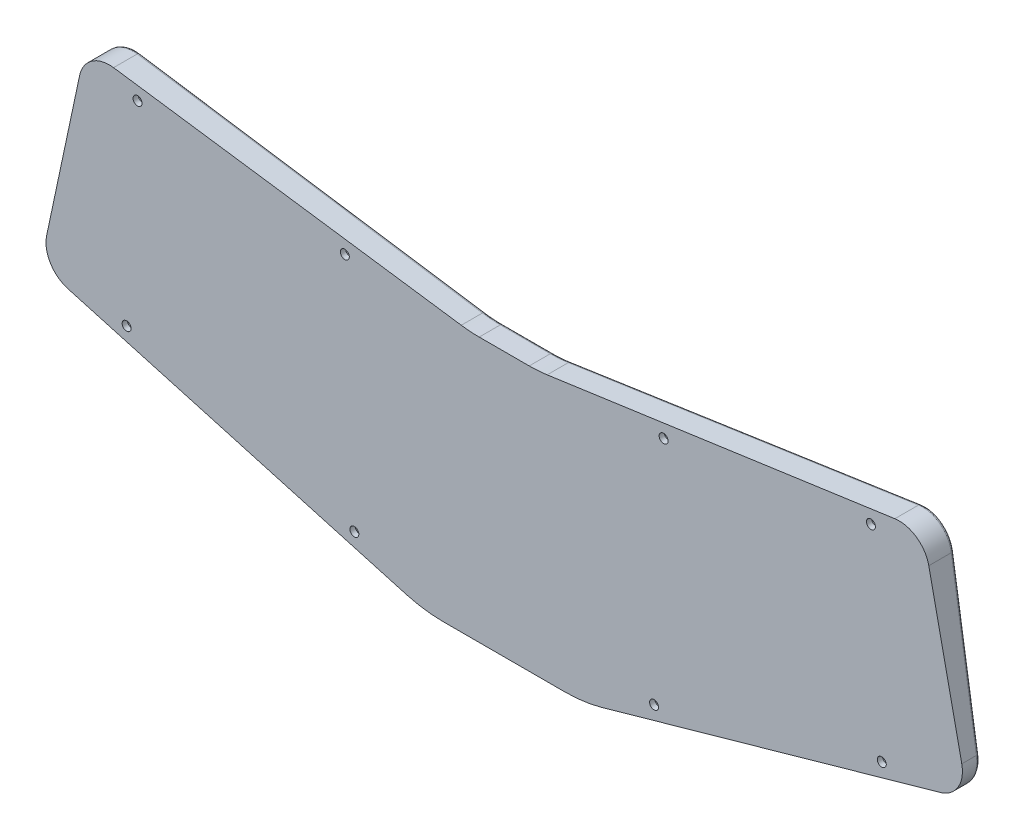
SolidWorks part; units mm, degrees
ref_plane "Front Plane" through (0, 0, 0) normal (0, 0, 1) x (1, 0, 0)
ref_plane "Top Plane" through (0, 0, 0) normal (0, 1, 0) x (1, 0, 0)
ref_plane "Right Plane" through (0, 0, 0) normal (1, 0, 0) x (0, 0, -1)
sketch "Model" plane through (0, 0, 0) normal (0, 0, 1) x (1, 0, 0)
  line L0 (7.1929, 63.9009) -> (19.4198, 61.302)
  line L1 (19.9974, 60.4125) -> (17.3986, 48.1856)
  line L2 (16.509, 47.6079) -> (4.2822, 50.2068)
  line L3 (3.7045, 51.0964) -> (6.3034, 63.3232)
  line L4 (3.2426, 45.3161) -> (15.4694, 42.7172)
  line L5 (16.0471, 41.8276) -> (13.4482, 29.6008)
  line L6 (12.5587, 29.0231) -> (0.3318, 31.622)
  line L7 (-0.2458, 32.5116) -> (2.3531, 44.7384)
  line L8 (-0.7077, 26.7313) -> (11.5191, 24.1324)
  line L9 (12.0968, 23.2428) -> (9.4979, 11.016)
  line L10 (8.6084, 10.4383) -> (-3.6185, 13.0372)
  line L11 (-4.1962, 13.9268) -> (-1.5973, 26.1536)
  line L12 (26.1936, 61.9069) -> (38.4204, 59.308)
  line L13 (38.9981, 58.4184) -> (36.3992, 46.1916)
  line L14 (35.5096, 45.6139) -> (23.2828, 48.2128)
  line L15 (22.7051, 49.1023) -> (25.304, 61.3292)
  line L16 (22.2432, 43.3221) -> (34.4701, 40.7232)
  line L17 (35.0478, 39.8336) -> (32.4489, 27.6068)
  line L18 (31.5593, 27.0291) -> (19.3325, 29.628)
  line L19 (18.7548, 30.5175) -> (21.3537, 42.7444)
  line L20 (18.2929, 24.7373) -> (30.5198, 22.1384)
  line L21 (31.0974, 21.2488) -> (28.4985, 9.022)
  line L22 (27.609, 8.4443) -> (15.3821, 11.0432)
  line L23 (14.8045, 11.9327) -> (17.4034, 24.1596)
  line L24 (45.2981, 60.4019) -> (57.525, 57.803)
  line L25 (58.1027, 56.9135) -> (55.5038, 44.6866)
  line L26 (54.6142, 44.109) -> (42.3874, 46.7078)
  line L27 (41.8097, 47.5974) -> (44.4086, 59.8242)
  line L28 (41.3478, 41.8171) -> (53.5747, 39.2182)
  line L29 (54.1523, 38.3287) -> (51.5534, 26.1018)
  line L30 (50.6639, 25.5241) -> (38.4371, 28.123)
  line L31 (37.8594, 29.0126) -> (40.4583, 41.2394)
  line L32 (37.3975, 23.2323) -> (49.6243, 20.6334)
  line L33 (50.202, 19.7439) -> (47.6031, 7.517)
  line L34 (46.7136, 6.9393) -> (34.4867, 9.5382)
  line L35 (33.9091, 10.4278) -> (36.5079, 22.6546)
  line L36 (64.4027, 58.897) -> (76.6296, 56.2981)
  line L37 (77.2072, 55.4085) -> (74.6083, 43.1817)
  line L38 (73.7188, 42.604) -> (61.492, 45.2029)
  line L39 (60.9143, 46.0924) -> (63.5132, 58.3193)
  line L40 (60.4524, 40.3122) -> (72.6792, 37.7133)
  line L41 (73.2569, 36.8237) -> (70.658, 24.5969)
  line L42 (69.7685, 24.0192) -> (57.5416, 26.6181)
  line L43 (56.964, 27.5076) -> (59.5629, 39.7345)
  line L44 (56.5021, 21.7274) -> (68.7289, 19.1285)
  line L45 (69.3066, 18.2389) -> (66.7077, 6.0121)
  line L46 (65.8182, 5.4344) -> (53.5913, 8.0333)
  line L47 (53.0136, 8.9228) -> (55.6125, 21.1497)
  line L48 (52.5518, 3.1425) -> (64.7786, 0.5437)
  line L49 (65.3563, -0.3459) -> (62.7574, -12.5727)
  line L50 (61.8678, -13.1504) -> (49.641, -10.5515)
  line L51 (49.0633, -9.662) -> (51.6622, 2.5649)
  line L52 (82.4677, 52.5013) -> (94.6946, 49.9024)
  line L53 (95.2723, 49.0128) -> (92.6734, 36.786)
  line L54 (91.7838, 36.2083) -> (79.557, 38.8072)
  line L55 (78.9793, 39.6967) -> (81.5782, 51.9236)
  line L56 (78.5174, 33.9165) -> (90.7443, 31.3176)
  line L57 (91.3219, 30.428) -> (88.723, 18.2012)
  line L58 (87.8335, 17.6235) -> (75.6067, 20.2224)
  line L59 (75.029, 21.1119) -> (77.6279, 33.3388)
  line L60 (74.5671, 15.3317) -> (86.7939, 12.7328)
  line L61 (87.3716, 11.8432) -> (84.7727, -0.3836)
  line L62 (83.8832, -0.9613) -> (71.6563, 1.6376)
  line L63 (71.0787, 2.5271) -> (73.6776, 14.754)
  line L64 (101.4684, 50.5072) -> (113.6952, 47.9083)
  line L65 (114.2729, 47.0188) -> (111.674, 34.792)
  line L66 (110.7845, 34.2143) -> (98.5576, 36.8132)
  line L67 (97.9799, 37.7027) -> (100.5788, 49.9296)
  line L68 (97.5181, 31.9224) -> (109.7449, 29.3235)
  line L69 (110.3226, 28.434) -> (107.7237, 16.2072)
  line L70 (106.8341, 15.6295) -> (94.6073, 18.2284)
  line L71 (94.0296, 19.1179) -> (96.6285, 31.3448)
  line L72 (93.5677, 13.3376) -> (105.7946, 10.7387)
  line L73 (106.3723, 9.8492) -> (103.7734, -2.3777)
  line L74 (102.8838, -2.9553) -> (90.657, -0.3564)
  line L75 (90.0793, 0.5331) -> (92.6782, 12.76)
  line L76 (134.1052, 48.9374) -> (131.5063, 36.7105)
  line L77 (130.6167, 36.1328) -> (118.3899, 38.7317)
  line L78 (117.8122, 39.6213) -> (120.4111, 51.8481)
  line L79 (117.3503, 33.841) -> (129.5772, 31.2421)
  line L80 (130.1548, 30.3526) -> (127.556, 18.1257)
  line L81 (126.6664, 17.548) -> (114.4396, 20.1469)
  line L82 (113.8619, 21.0365) -> (116.4608, 33.2633)
  line L83 (113.4, 15.2562) -> (125.6268, 12.6573)
  line L84 (126.2045, 11.7678) -> (123.6056, -0.4591)
  line L85 (122.7161, -1.0368) -> (110.4892, 1.5621)
  line L86 (109.9116, 2.4517) -> (112.5105, 14.6785)
  line L87 (70.6168, -3.2531) -> (82.8436, -5.852)
  line L88 (83.4213, -6.7416) -> (80.8224, -18.9684)
  line L89 (79.9329, -19.5461) -> (67.706, -16.9472)
  line L90 (67.1283, -16.0577) -> (69.7272, -3.8308)
  line L91 (89.6174, -5.2472) -> (101.8443, -7.8461)
  line L92 (102.4219, -8.7356) -> (99.823, -20.9625)
  line L93 (98.9335, -21.5401) -> (86.7066, -18.9412)
  line L94 (86.129, -18.0517) -> (88.7279, -5.8248)
  line L95 (117.654, -29.3648) -> (112.0852, -26.5274)
  line L96 (111.7574, -25.5186) -> (117.4323, -14.381)
  line L97 (118.4411, -14.0533) -> (129.5787, -19.7282)
  line L98 (129.9064, -20.7369) -> (124.2315, -31.8745)
  line L99 (123.2228, -32.2023) -> (117.654, -29.3648)
  line L100 (112.629, -33.5493) -> (124.2783, -36.8388)
  line L101 (137.0504, -38.6074) -> (160.1264, -38.6074)
  line L102 (160.1264, -38.6074) -> (183.2025, -38.6074)
  line L103 (195.9746, -36.8388) -> (207.6239, -33.5493)
  line L104 (226.4824, -28.2242) -> (271.949, -15.3856)
  line L105 (271.949, -15.3856) -> (293.9202, -9.1816)
  line L106 (210.7632, 57.9332) -> (177.0346, 53.1572)
  line L107 (169.604, 52.6338) -> (150.6488, 52.6338)
  line L108 (143.2182, 53.1572) -> (109.4896, 57.9332)
  line L109 (90.0873, 60.6806) -> (30.9176, 69.0589)
  line L110 (289.3352, 69.0589) -> (230.1656, 60.6806)
  line L111 (26.3327, -9.1816) -> (48.3039, -15.3856)
  line L112 (48.3039, -15.3856) -> (93.7705, -28.2242)
  line L113 (312.7787, -3.8564) -> (324.1811, -0.6367)
  line L114 (-2.1254, 39.3007) -> (3.622, 66.34)
  line L115 (-2.1254, 39.3007) -> (-8.8731, 7.5553)
  line L116 (13.8071, 71.4818) -> (11.4504, 71.8155)
  line L117 (-3.9283, -0.6367) -> (7.4742, -3.8564)
  line L118 (306.4458, 71.4818) -> (308.8024, 71.8155)
  line L119 (322.3782, 39.3007) -> (329.1259, 7.5553)
  line L120 (322.3782, 39.3007) -> (316.6308, 66.34)
  line L121 (121.3006, 52.4258) -> (133.5275, 49.8269)
  line L122 (313.0599, 63.9009) -> (300.8331, 61.302)
  line L123 (300.2554, 60.4125) -> (302.8543, 48.1856)
  line L124 (303.7438, 47.6079) -> (315.9707, 50.2068)
  line L125 (316.5483, 51.0964) -> (313.9494, 63.3232)
  line L126 (317.0102, 45.3161) -> (304.7834, 42.7172)
  line L127 (304.2057, 41.8276) -> (306.8046, 29.6008)
  line L128 (307.6941, 29.0231) -> (319.921, 31.622)
  line L129 (320.4987, 32.5116) -> (317.8998, 44.7384)
  line L130 (320.9605, 26.7313) -> (308.7337, 24.1324)
  line L131 (308.156, 23.2428) -> (310.7549, 11.016)
  line L132 (311.6445, 10.4383) -> (323.8713, 13.0372)
  line L133 (324.449, 13.9268) -> (321.8501, 26.1536)
  line L134 (294.0593, 61.9069) -> (281.8324, 59.308)
  line L135 (281.2548, 58.4184) -> (283.8536, 46.1916)
  line L136 (284.7432, 45.6139) -> (296.97, 48.2128)
  line L137 (297.5477, 49.1023) -> (294.9488, 61.3292)
  line L138 (298.0096, 43.3221) -> (285.7828, 40.7232)
  line L139 (285.2051, 39.8336) -> (287.804, 27.6068)
  line L140 (288.6935, 27.0291) -> (300.9204, 29.628)
  line L141 (301.498, 30.5175) -> (298.8991, 42.7444)
  line L142 (301.9599, 24.7373) -> (289.7331, 22.1384)
  line L143 (289.1554, 21.2488) -> (291.7543, 9.022)
  line L144 (292.6438, 8.4443) -> (304.8707, 11.0432)
  line L145 (305.4484, 11.9327) -> (302.8495, 24.1596)
  line L146 (274.9547, 60.4019) -> (262.7278, 57.803)
  line L147 (262.1502, 56.9135) -> (264.7491, 44.6866)
  line L148 (265.6386, 44.109) -> (277.8655, 46.7078)
  line L149 (278.4431, 47.5974) -> (275.8442, 59.8242)
  line L150 (278.905, 41.8171) -> (266.6782, 39.2182)
  line L151 (266.1005, 38.3287) -> (268.6994, 26.1018)
  line L152 (269.5889, 25.5241) -> (281.8158, 28.123)
  line L153 (282.3935, 29.0126) -> (279.7946, 41.2394)
  line L154 (282.8553, 23.2323) -> (270.6285, 20.6334)
  line L155 (270.0508, 19.7439) -> (272.6497, 7.517)
  line L156 (273.5393, 6.9393) -> (285.7661, 9.5382)
  line L157 (286.3438, 10.4278) -> (283.7449, 22.6546)
  line L158 (255.8501, 58.897) -> (243.6233, 56.2981)
  line L159 (243.0456, 55.4085) -> (245.6445, 43.1817)
  line L160 (246.534, 42.604) -> (258.7609, 45.2029)
  line L161 (259.3385, 46.0924) -> (256.7397, 58.3193)
  line L162 (259.8004, 40.3122) -> (247.5736, 37.7133)
  line L163 (246.9959, 36.8237) -> (249.5948, 24.5969)
  line L164 (250.4843, 24.0192) -> (262.7112, 26.6181)
  line L165 (263.2889, 27.5076) -> (260.69, 39.7345)
  line L166 (263.7508, 21.7274) -> (251.5239, 19.1285)
  line L167 (250.9462, 18.2389) -> (253.5451, 6.0121)
  line L168 (254.4347, 5.4344) -> (266.6615, 8.0333)
  line L169 (267.2392, 8.9228) -> (264.6403, 21.1497)
  line L170 (267.7011, 3.1425) -> (255.4742, 0.5437)
  line L171 (254.8966, -0.3459) -> (257.4954, -12.5727)
  line L172 (258.385, -13.1504) -> (270.6118, -10.5515)
  line L173 (271.1895, -9.662) -> (268.5906, 2.5649)
  line L174 (237.7851, 52.5013) -> (225.5582, 49.9024)
  line L175 (224.9806, 49.0128) -> (227.5795, 36.786)
  line L176 (228.469, 36.2083) -> (240.6958, 38.8072)
  line L177 (241.2735, 39.6967) -> (238.6746, 51.9236)
  line L178 (241.7354, 33.9165) -> (229.5086, 31.3176)
  line L179 (228.9309, 30.428) -> (231.5298, 18.2012)
  line L180 (232.4193, 17.6235) -> (244.6462, 20.2224)
  line L181 (245.2238, 21.1119) -> (242.6249, 33.3388)
  line L182 (245.6857, 15.3317) -> (233.4589, 12.7328)
  line L183 (232.8812, 11.8432) -> (235.4801, -0.3836)
  line L184 (236.3696, -0.9613) -> (248.5965, 1.6376)
  line L185 (249.1742, 2.5271) -> (246.5753, 14.754)
  line L186 (218.7845, 50.5072) -> (206.5576, 47.9083)
  line L187 (205.9799, 47.0188) -> (208.5788, 34.792)
  line L188 (209.4684, 34.2143) -> (221.6952, 36.8132)
  line L189 (222.2729, 37.7027) -> (219.674, 49.9296)
  line L190 (222.7348, 31.9224) -> (210.5079, 29.3235)
  line L191 (209.9303, 28.434) -> (212.5292, 16.2072)
  line L192 (213.4187, 15.6295) -> (225.6455, 18.2284)
  line L193 (226.2232, 19.1179) -> (223.6243, 31.3448)
  line L194 (226.6851, 13.3376) -> (214.4583, 10.7387)
  line L195 (213.8806, 9.8492) -> (216.4795, -2.3777)
  line L196 (217.369, -2.9553) -> (229.5959, -0.3564)
  line L197 (230.1735, 0.5331) -> (227.5746, 12.76)
  line L198 (186.1477, 48.9374) -> (188.7466, 36.7105)
  line L199 (189.6361, 36.1328) -> (201.8629, 38.7317)
  line L200 (202.4406, 39.6213) -> (199.8417, 51.8481)
  line L201 (202.9025, 33.841) -> (190.6757, 31.2421)
  line L202 (190.098, 30.3526) -> (192.6969, 18.1257)
  line L203 (193.5864, 17.548) -> (205.8133, 20.1469)
  line L204 (206.3909, 21.0365) -> (203.792, 33.2633)
  line L205 (206.8528, 15.2562) -> (194.626, 12.6573)
  line L206 (194.0483, 11.7678) -> (196.6472, -0.4591)
  line L207 (197.5367, -1.0368) -> (209.7636, 1.5621)
  line L208 (210.3413, 2.4517) -> (207.7424, 14.6785)
  line L209 (249.636, -3.2531) -> (237.4092, -5.852)
  line L210 (236.8315, -6.7416) -> (239.4304, -18.9684)
  line L211 (240.32, -19.5461) -> (252.5468, -16.9472)
  line L212 (253.1245, -16.0577) -> (250.5256, -3.8308)
  line L213 (230.6354, -5.2472) -> (218.4086, -7.8461)
  line L214 (217.8309, -8.7356) -> (220.4298, -20.9625)
  line L215 (221.3193, -21.5401) -> (233.5462, -18.9412)
  line L216 (234.1239, -18.0517) -> (231.525, -5.8248)
  line L217 (202.5988, -29.3648) -> (208.1676, -26.5274)
  line L218 (208.4954, -25.5186) -> (202.8205, -14.381)
  line L219 (201.8118, -14.0533) -> (190.6742, -19.7282)
  line L220 (190.3464, -20.7369) -> (196.0213, -31.8745)
  line L221 (197.03, -32.2023) -> (202.5988, -29.3648)
  line L222 (198.9522, 52.4258) -> (186.7253, 49.8269)
  line L223 (169.604, 55.6338) -> (150.6488, 55.6338)
  line L224 (143.6388, 56.1276) -> (11.8711, 74.7858)
  line L225 (0.6876, 66.9637) -> (-5.0598, 39.9244)
  line L226 (-5.0598, 39.9244) -> (-11.8075, 8.179)
  line L227 (-4.7435, -3.5238) -> (47.4886, -18.2727)
  line L228 (47.4886, -18.2727) -> (123.463, -39.7259)
  line L229 (137.0504, -41.6074) -> (160.1264, -41.6074)
  line L230 (160.1264, -41.6074) -> (183.2025, -41.6074)
  line L231 (196.7898, -39.7259) -> (272.7642, -18.2727)
  line L232 (272.7642, -18.2727) -> (324.9963, -3.5238)
  line L233 (332.0603, 8.179) -> (325.3126, 39.9244)
  line L234 (325.3126, 39.9244) -> (319.5653, 66.9637)
  line L235 (308.3818, 74.7858) -> (176.614, 56.1276)
  line L236 (169.604, 57.1338) -> (150.6488, 57.1338)
  line L237 (143.8491, 57.6128) -> (12.0814, 76.271)
  line L238 (-0.7797, 67.2756) -> (-6.527, 40.2363)
  line L239 (-6.527, 40.2363) -> (-13.2747, 8.4909)
  line L240 (-5.1511, -4.9673) -> (47.081, -19.7163)
  line L241 (47.081, -19.7163) -> (123.0554, -41.1694)
  line L242 (137.0504, -43.1074) -> (160.1264, -43.1074)
  line L243 (160.1264, -43.1074) -> (183.2025, -43.1074)
  line L244 (197.1974, -41.1694) -> (273.1718, -19.7163)
  line L245 (273.1718, -19.7163) -> (325.404, -4.9673)
  line L246 (333.5276, 8.4909) -> (326.7799, 40.2363)
  line L247 (326.7799, 40.2363) -> (321.0325, 67.2756)
  line L248 (308.1715, 76.271) -> (176.4037, 57.6128)
  arc A0 (106.6702, -28.8979) -> (101.2821, -27.3764) centre (103.1997, -30.8868) ccw
  arc A1 (93.7705, -28.2242) -> (101.2821, -27.3764) centre (96.4879, -18.6005) ccw
  arc A2 (106.6702, -28.8979) -> (112.629, -33.5493) centre (115.3464, -23.9256) ccw
  circle A3 centre (103.3356, -30.4056) radius 1.7
  arc A4 (207.6239, -33.5493) -> (213.5826, -28.8979) centre (204.9064, -23.9256) ccw
  arc A5 (218.9708, -27.3764) -> (226.4824, -28.2242) centre (223.7649, -18.6005) ccw
  arc A6 (218.9708, -27.3764) -> (213.5826, -28.8979) centre (217.0531, -30.8868) ccw
  circle A7 centre (216.9173, -30.4056) radius 1.7
  arc A8 (218.0932, 56.0855) -> (223.6367, 56.8704) centre (220.4644, 59.3069) ccw
  arc A9 (96.6161, 56.8704) -> (102.1596, 56.0855) centre (99.7884, 59.3069) ccw
  arc A10 (109.4896, 57.9332) -> (102.1596, 56.0855) centre (108.0876, 48.032) ccw
  arc A11 (96.6161, 56.8704) -> (90.0873, 60.6806) centre (88.6852, 50.7793) ccw
  arc A12 (218.0932, 56.0855) -> (210.7632, 57.9332) centre (212.1652, 48.032) ccw
  arc A13 (230.1656, 60.6806) -> (223.6367, 56.8704) centre (231.5676, 50.7793) ccw
  circle A14 centre (99.7183, 58.8118) radius 1.7
  circle A15 centre (220.5345, 58.8118) radius 1.7
  arc A16 (305.2671, -3.0086) -> (299.8789, -4.5301) centre (303.3494, -6.519) ccw
  arc A17 (20.3739, -4.5301) -> (14.9858, -3.0086) centre (16.9034, -6.519) ccw
  arc A18 (20.3739, -4.5301) -> (26.3327, -9.1816) centre (29.0501, 0.4421) ccw
  arc A19 (305.2671, -3.0086) -> (312.7787, -3.8564) centre (310.0612, 5.7673) ccw
  arc A20 (293.9202, -9.1816) -> (299.8789, -4.5301) centre (291.2027, 0.4421) ccw
  arc A21 (7.4742, -3.8564) -> (14.9858, -3.0086) centre (10.1916, 5.7673) ccw
  circle A22 centre (17.0393, -6.0378) radius 1.7
  circle A23 centre (303.2135, -6.0378) radius 1.7
  arc A24 (-8.8731, 7.5553) -> (-3.9283, -0.6367) centre (-2.026, 6.0999) ccw
  arc A25 (11.4504, 71.8155) -> (3.622, 66.34) centre (10.469, 64.8846) ccw
  arc A26 (316.6308, 66.34) -> (308.8024, 71.8155) centre (309.7838, 64.8846) ccw
  arc A27 (324.1811, -0.6367) -> (329.1259, 7.5553) centre (322.2789, 6.0999) ccw
  arc A28 (296.6652, 67.2112) -> (302.641, 68.6986) centre (299.0364, 70.4326) ccw
  arc A29 (17.6118, 68.6986) -> (23.5876, 67.2112) centre (21.2165, 70.4326) ccw
  arc A30 (30.9176, 69.0589) -> (23.5876, 67.2112) centre (29.5156, 59.1577) ccw
  arc A31 (17.6118, 68.6986) -> (13.8071, 71.4818) centre (13.106, 66.5312) ccw
  arc A32 (306.4458, 71.4818) -> (302.641, 68.6986) centre (307.1468, 66.5312) ccw
  arc A33 (296.6652, 67.2112) -> (289.3352, 69.0589) centre (290.7372, 59.1577) ccw
  circle A34 centre (299.1065, 69.9376) radius 1.7
  circle A35 centre (21.1705, 69.9376) radius 1.7
  arc A36 (3.7045, 51.0964) -> (4.2822, 50.2068) centre (4.4381, 50.9404) ccw
  arc A37 (7.1929, 63.9009) -> (6.3034, 63.3232) centre (7.037, 63.1673) ccw
  arc A38 (19.9974, 60.4125) -> (19.4198, 61.302) centre (19.2638, 60.5684) ccw
  arc A39 (16.509, 47.6079) -> (17.3986, 48.1856) centre (16.6649, 48.3415) ccw
  arc A40 (3.2426, 45.3161) -> (2.3531, 44.7384) centre (3.0867, 44.5825) ccw
  arc A41 (-0.2458, 32.5116) -> (0.3318, 31.622) centre (0.4878, 32.3556) ccw
  arc A42 (12.5587, 29.0231) -> (13.4482, 29.6008) centre (12.7146, 29.7567) ccw
  arc A43 (16.0471, 41.8276) -> (15.4694, 42.7172) centre (15.3135, 41.9836) ccw
  arc A44 (-0.7077, 26.7313) -> (-1.5973, 26.1536) centre (-0.8637, 25.9977) ccw
  arc A45 (-4.1962, 13.9268) -> (-3.6185, 13.0372) centre (-3.4625, 13.7708) ccw
  arc A46 (8.6084, 10.4383) -> (9.4979, 11.016) centre (8.7643, 11.1719) ccw
  arc A47 (12.0968, 23.2428) -> (11.5191, 24.1324) centre (11.3632, 23.3988) ccw
  arc A48 (14.8045, 11.9327) -> (15.3821, 11.0432) centre (15.5381, 11.7768) ccw
  arc A49 (27.609, 8.4443) -> (28.4985, 9.022) centre (27.7649, 9.1779) ccw
  arc A50 (31.0974, 21.2488) -> (30.5198, 22.1384) centre (30.3638, 21.4048) ccw
  arc A51 (18.2929, 24.7373) -> (17.4034, 24.1596) centre (18.137, 24.0036) ccw
  arc A52 (18.7548, 30.5175) -> (19.3325, 29.628) centre (19.4884, 30.3616) ccw
  arc A53 (31.5593, 27.0291) -> (32.4489, 27.6068) centre (31.7152, 27.7627) ccw
  arc A54 (35.0478, 39.8336) -> (34.4701, 40.7232) centre (34.3141, 39.9896) ccw
  arc A55 (22.2432, 43.3221) -> (21.3537, 42.7444) centre (22.0873, 42.5885) ccw
  arc A56 (22.7051, 49.1023) -> (23.2828, 48.2128) centre (23.4387, 48.9464) ccw
  arc A57 (35.5096, 45.6139) -> (36.3992, 46.1916) centre (35.6656, 46.3475) ccw
  arc A58 (38.9981, 58.4184) -> (38.4204, 59.308) centre (38.2645, 58.5744) ccw
  arc A59 (26.1936, 61.9069) -> (25.304, 61.3292) centre (26.0376, 61.1733) ccw
  arc A60 (33.9091, 10.4278) -> (34.4867, 9.5382) centre (34.6427, 10.2718) ccw
  arc A61 (37.3975, 23.2323) -> (36.5079, 22.6546) centre (37.2416, 22.4987) ccw
  arc A62 (50.202, 19.7439) -> (49.6243, 20.6334) centre (49.4684, 19.8998) ccw
  arc A63 (46.7136, 6.9393) -> (47.6031, 7.517) centre (46.8695, 7.673) ccw
  arc A64 (50.6639, 25.5241) -> (51.5534, 26.1018) centre (50.8198, 26.2578) ccw
  arc A65 (37.8594, 29.0126) -> (38.4371, 28.123) centre (38.593, 28.8567) ccw
  arc A66 (41.3478, 41.8171) -> (40.4583, 41.2394) centre (41.1919, 41.0835) ccw
  arc A67 (54.1523, 38.3287) -> (53.5747, 39.2182) centre (53.4187, 38.4846) ccw
  arc A68 (54.6142, 44.109) -> (55.5038, 44.6866) centre (54.7702, 44.8426) ccw
  arc A69 (41.8097, 47.5974) -> (42.3874, 46.7078) centre (42.5433, 47.4415) ccw
  arc A70 (45.2981, 60.4019) -> (44.4086, 59.8242) centre (45.1422, 59.6683) ccw
  arc A71 (58.1027, 56.9135) -> (57.525, 57.803) centre (57.369, 57.0694) ccw
  arc A72 (56.964, 27.5076) -> (57.5416, 26.6181) centre (57.6976, 27.3517) ccw
  arc A73 (60.4524, 40.3122) -> (59.5629, 39.7345) centre (60.2965, 39.5785) ccw
  arc A74 (73.2569, 36.8237) -> (72.6792, 37.7133) centre (72.5233, 36.9797) ccw
  arc A75 (69.7685, 24.0192) -> (70.658, 24.5969) centre (69.9244, 24.7528) ccw
  arc A76 (60.9143, 46.0924) -> (61.492, 45.2029) centre (61.6479, 45.9365) ccw
  arc A77 (73.7188, 42.604) -> (74.6083, 43.1817) centre (73.8747, 43.3376) ccw
  arc A78 (77.2072, 55.4085) -> (76.6296, 56.2981) centre (76.4736, 55.5645) ccw
  arc A79 (64.4027, 58.897) -> (63.5132, 58.3193) centre (64.2468, 58.1634) ccw
  arc A80 (53.0136, 8.9228) -> (53.5913, 8.0333) centre (53.7472, 8.7669) ccw
  arc A81 (56.5021, 21.7274) -> (55.6125, 21.1497) centre (56.3461, 20.9937) ccw
  arc A82 (69.3066, 18.2389) -> (68.7289, 19.1285) centre (68.573, 18.3948) ccw
  arc A83 (65.8182, 5.4344) -> (66.7077, 6.0121) centre (65.9741, 6.168) ccw
  arc A84 (49.0633, -9.662) -> (49.641, -10.5515) centre (49.7969, -9.8179) ccw
  arc A85 (52.5518, 3.1425) -> (51.6622, 2.5649) centre (52.3958, 2.4089) ccw
  arc A86 (65.3563, -0.3459) -> (64.7786, 0.5437) centre (64.6227, -0.19) ccw
  arc A87 (61.8678, -13.1504) -> (62.7574, -12.5727) centre (62.0238, -12.4168) ccw
  arc A88 (67.1283, -16.0577) -> (67.706, -16.9472) centre (67.8619, -16.2136) ccw
  arc A89 (70.6168, -3.2531) -> (69.7272, -3.8308) centre (70.4608, -3.9868) ccw
  arc A90 (83.4213, -6.7416) -> (82.8436, -5.852) centre (82.6877, -6.5856) ccw
  arc A91 (79.9329, -19.5461) -> (80.8224, -18.9684) centre (80.0888, -18.8125) ccw
  arc A92 (71.0787, 2.5271) -> (71.6563, 1.6376) centre (71.8123, 2.3712) ccw
  arc A93 (83.8832, -0.9613) -> (84.7727, -0.3836) centre (84.0391, -0.2277) ccw
  arc A94 (87.3716, 11.8432) -> (86.7939, 12.7328) centre (86.638, 11.9992) ccw
  arc A95 (74.5671, 15.3317) -> (73.6776, 14.754) centre (74.4112, 14.5981) ccw
  arc A96 (75.029, 21.1119) -> (75.6067, 20.2224) centre (75.7626, 20.956) ccw
  arc A97 (87.8335, 17.6235) -> (88.723, 18.2012) centre (87.9894, 18.3571) ccw
  arc A98 (91.3219, 30.428) -> (90.7443, 31.3176) centre (90.5883, 30.584) ccw
  arc A99 (78.5174, 33.9165) -> (77.6279, 33.3388) centre (78.3615, 33.1829) ccw
  arc A100 (78.9793, 39.6967) -> (79.557, 38.8072) centre (79.7129, 39.5408) ccw
  arc A101 (82.4677, 52.5013) -> (81.5782, 51.9236) centre (82.3118, 51.7677) ccw
  arc A102 (95.2723, 49.0128) -> (94.6946, 49.9024) centre (94.5387, 49.1688) ccw
  arc A103 (91.7838, 36.2083) -> (92.6734, 36.786) centre (91.9398, 36.9419) ccw
  arc A104 (97.9799, 37.7027) -> (98.5576, 36.8132) centre (98.7135, 37.5468) ccw
  arc A105 (101.4684, 50.5072) -> (100.5788, 49.9296) centre (101.3124, 49.7736) ccw
  arc A106 (114.2729, 47.0188) -> (113.6952, 47.9083) centre (113.5393, 47.1747) ccw
  arc A107 (110.7845, 34.2143) -> (111.674, 34.792) centre (110.9404, 34.9479) ccw
  arc A108 (97.5181, 31.9224) -> (96.6285, 31.3448) centre (97.3621, 31.1888) ccw
  arc A109 (110.3226, 28.434) -> (109.7449, 29.3235) centre (109.589, 28.5899) ccw
  arc A110 (106.8341, 15.6295) -> (107.7237, 16.2072) centre (106.9901, 16.3631) ccw
  arc A111 (94.0296, 19.1179) -> (94.6073, 18.2284) centre (94.7632, 18.962) ccw
  arc A112 (93.5677, 13.3376) -> (92.6782, 12.76) centre (93.4118, 12.604) ccw
  arc A113 (106.3723, 9.8492) -> (105.7946, 10.7387) centre (105.6386, 10.0051) ccw
  arc A114 (102.8838, -2.9553) -> (103.7734, -2.3777) centre (103.0397, -2.2217) ccw
  arc A115 (90.0793, 0.5331) -> (90.657, -0.3564) centre (90.8129, 0.3772) ccw
  arc A116 (89.6174, -5.2472) -> (88.7279, -5.8248) centre (89.4615, -5.9808) ccw
  arc A117 (102.4219, -8.7356) -> (101.8443, -7.8461) centre (101.6883, -8.5797) ccw
  arc A118 (98.9335, -21.5401) -> (99.823, -20.9625) centre (99.0894, -20.8065) ccw
  arc A119 (86.129, -18.0517) -> (86.7066, -18.9412) centre (86.8626, -18.2076) ccw
  arc A120 (111.7574, -25.5186) -> (112.0852, -26.5274) centre (112.4257, -25.8591) ccw
  arc A121 (118.4411, -14.0533) -> (117.4323, -14.381) centre (118.1006, -14.7215) ccw
  arc A122 (129.9064, -20.7369) -> (129.5787, -19.7282) centre (129.2382, -20.3964) ccw
  arc A123 (123.2228, -32.2023) -> (124.2315, -31.8745) centre (123.5633, -31.534) ccw
  arc A124 (109.9116, 2.4517) -> (110.4892, 1.5621) centre (110.6452, 2.2957) ccw
  arc A125 (122.7161, -1.0368) -> (123.6056, -0.4591) centre (122.872, -0.3032) ccw
  arc A126 (126.2045, 11.7678) -> (125.6268, 12.6573) centre (125.4709, 11.9237) ccw
  arc A127 (113.4, 15.2562) -> (112.5105, 14.6785) centre (113.2441, 14.5226) ccw
  arc A128 (113.8619, 21.0365) -> (114.4396, 20.1469) centre (114.5955, 20.8805) ccw
  arc A129 (126.6664, 17.548) -> (127.556, 18.1257) centre (126.8223, 18.2817) ccw
  arc A130 (130.1548, 30.3526) -> (129.5772, 31.2421) centre (129.4212, 30.5085) ccw
  arc A131 (117.3503, 33.841) -> (116.4608, 33.2633) centre (117.1944, 33.1074) ccw
  arc A132 (117.8122, 39.6213) -> (118.3899, 38.7317) centre (118.5458, 39.4654) ccw
  arc A133 (130.6167, 36.1328) -> (131.5063, 36.7105) centre (130.7727, 36.8665) ccw
  arc A134 (134.1052, 48.9374) -> (133.5275, 49.8269) centre (133.3716, 49.0933) ccw
  arc A135 (121.3006, 52.4258) -> (120.4111, 51.8481) centre (121.1447, 51.6922) ccw
  arc A136 (313.9494, 63.3232) -> (313.0599, 63.9009) centre (313.2158, 63.1673) ccw
  arc A137 (300.8331, 61.302) -> (300.2554, 60.4125) centre (300.989, 60.5684) ccw
  arc A138 (302.8543, 48.1856) -> (303.7438, 47.6079) centre (303.5879, 48.3415) ccw
  arc A139 (315.9707, 50.2068) -> (316.5483, 51.0964) centre (315.8147, 50.9404) ccw
  arc A140 (317.8998, 44.7384) -> (317.0102, 45.3161) centre (317.1662, 44.5825) ccw
  arc A141 (304.7834, 42.7172) -> (304.2057, 41.8276) centre (304.9393, 41.9836) ccw
  arc A142 (306.8046, 29.6008) -> (307.6941, 29.0231) centre (307.5382, 29.7567) ccw
  arc A143 (319.921, 31.622) -> (320.4987, 32.5116) centre (319.7651, 32.3556) ccw
  arc A144 (321.8501, 26.1536) -> (320.9605, 26.7313) centre (321.1165, 25.9977) ccw
  arc A145 (308.7337, 24.1324) -> (308.156, 23.2428) centre (308.8896, 23.3988) ccw
  arc A146 (310.7549, 11.016) -> (311.6445, 10.4383) centre (311.4885, 11.1719) ccw
  arc A147 (323.8713, 13.0372) -> (324.449, 13.9268) centre (323.7154, 13.7708) ccw
  arc A148 (294.9488, 61.3292) -> (294.0593, 61.9069) centre (294.2152, 61.1733) ccw
  arc A149 (281.8324, 59.308) -> (281.2548, 58.4184) centre (281.9884, 58.5744) ccw
  arc A150 (283.8536, 46.1916) -> (284.7432, 45.6139) centre (284.5873, 46.3475) ccw
  arc A151 (296.97, 48.2128) -> (297.5477, 49.1023) centre (296.8141, 48.9464) ccw
  arc A152 (298.8991, 42.7444) -> (298.0096, 43.3221) centre (298.1655, 42.5885) ccw
  arc A153 (285.7828, 40.7232) -> (285.2051, 39.8336) centre (285.9387, 39.9896) ccw
  arc A154 (287.804, 27.6068) -> (288.6935, 27.0291) centre (288.5376, 27.7627) ccw
  arc A155 (300.9204, 29.628) -> (301.498, 30.5175) centre (300.7644, 30.3616) ccw
  arc A156 (302.8495, 24.1596) -> (301.9599, 24.7373) centre (302.1159, 24.0036) ccw
  arc A157 (289.7331, 22.1384) -> (289.1554, 21.2488) centre (289.889, 21.4048) ccw
  arc A158 (291.7543, 9.022) -> (292.6438, 8.4443) centre (292.4879, 9.1779) ccw
  arc A159 (304.8707, 11.0432) -> (305.4484, 11.9327) centre (304.7147, 11.7768) ccw
  arc A160 (262.7278, 57.803) -> (262.1502, 56.9135) centre (262.8838, 57.0694) ccw
  arc A161 (275.8442, 59.8242) -> (274.9547, 60.4019) centre (275.1106, 59.6683) ccw
  arc A162 (264.7491, 44.6866) -> (265.6386, 44.109) centre (265.4827, 44.8426) ccw
  arc A163 (277.8655, 46.7078) -> (278.4431, 47.5974) centre (277.7095, 47.4415) ccw
  arc A164 (266.6782, 39.2182) -> (266.1005, 38.3287) centre (266.8341, 38.4846) ccw
  arc A165 (279.7946, 41.2394) -> (278.905, 41.8171) centre (279.0609, 41.0835) ccw
  arc A166 (268.6994, 26.1018) -> (269.5889, 25.5241) centre (269.433, 26.2578) ccw
  arc A167 (281.8158, 28.123) -> (282.3935, 29.0126) centre (281.6598, 28.8567) ccw
  arc A168 (270.6285, 20.6334) -> (270.0508, 19.7439) centre (270.7844, 19.8998) ccw
  arc A169 (283.7449, 22.6546) -> (282.8553, 23.2323) centre (283.0113, 22.4987) ccw
  arc A170 (272.6497, 7.517) -> (273.5393, 6.9393) centre (273.3833, 7.673) ccw
  arc A171 (285.7661, 9.5382) -> (286.3438, 10.4278) centre (285.6102, 10.2718) ccw
  arc A172 (256.7397, 58.3193) -> (255.8501, 58.897) centre (256.006, 58.1634) ccw
  arc A173 (243.6233, 56.2981) -> (243.0456, 55.4085) centre (243.7792, 55.5645) ccw
  arc A174 (245.6445, 43.1817) -> (246.534, 42.604) centre (246.3781, 43.3376) ccw
  arc A175 (258.7609, 45.2029) -> (259.3385, 46.0924) centre (258.6049, 45.9365) ccw
  arc A176 (247.5736, 37.7133) -> (246.9959, 36.8237) centre (247.7295, 36.9797) ccw
  arc A177 (260.69, 39.7345) -> (259.8004, 40.3122) centre (259.9564, 39.5785) ccw
  arc A178 (249.5948, 24.5969) -> (250.4843, 24.0192) centre (250.3284, 24.7528) ccw
  arc A179 (262.7112, 26.6181) -> (263.2889, 27.5076) centre (262.5553, 27.3517) ccw
  arc A180 (251.5239, 19.1285) -> (250.9462, 18.2389) centre (251.6798, 18.3948) ccw
  arc A181 (253.5451, 6.0121) -> (254.4347, 5.4344) centre (254.2787, 6.168) ccw
  arc A182 (264.6403, 21.1497) -> (263.7508, 21.7274) centre (263.9067, 20.9937) ccw
  arc A183 (266.6615, 8.0333) -> (267.2392, 8.9228) centre (266.5056, 8.7669) ccw
  arc A184 (255.4742, 0.5437) -> (254.8966, -0.3459) centre (255.6302, -0.19) ccw
  arc A185 (257.4954, -12.5727) -> (258.385, -13.1504) centre (258.2291, -12.4168) ccw
  arc A186 (268.5906, 2.5649) -> (267.7011, 3.1425) centre (267.857, 2.4089) ccw
  arc A187 (270.6118, -10.5515) -> (271.1895, -9.662) centre (270.4559, -9.8179) ccw
  arc A188 (225.5582, 49.9024) -> (224.9806, 49.0128) centre (225.7142, 49.1688) ccw
  arc A189 (238.6746, 51.9236) -> (237.7851, 52.5013) centre (237.941, 51.7677) ccw
  arc A190 (227.5795, 36.786) -> (228.469, 36.2083) centre (228.3131, 36.9419) ccw
  arc A191 (240.6958, 38.8072) -> (241.2735, 39.6967) centre (240.5399, 39.5408) ccw
  arc A192 (242.6249, 33.3388) -> (241.7354, 33.9165) centre (241.8913, 33.1829) ccw
  arc A193 (229.5086, 31.3176) -> (228.9309, 30.428) centre (229.6645, 30.584) ccw
  arc A194 (231.5298, 18.2012) -> (232.4193, 17.6235) centre (232.2634, 18.3571) ccw
  arc A195 (244.6462, 20.2224) -> (245.2238, 21.1119) centre (244.4902, 20.956) ccw
  arc A196 (246.5753, 14.754) -> (245.6857, 15.3317) centre (245.8417, 14.5981) ccw
  arc A197 (233.4589, 12.7328) -> (232.8812, 11.8432) centre (233.6148, 11.9992) ccw
  arc A198 (235.4801, -0.3836) -> (236.3696, -0.9613) centre (236.2137, -0.2277) ccw
  arc A199 (248.5965, 1.6376) -> (249.1742, 2.5271) centre (248.4406, 2.3712) ccw
  arc A200 (206.5576, 47.9083) -> (205.9799, 47.0188) centre (206.7135, 47.1747) ccw
  arc A201 (219.674, 49.9296) -> (218.7845, 50.5072) centre (218.9404, 49.7736) ccw
  arc A202 (208.5788, 34.792) -> (209.4684, 34.2143) centre (209.3124, 34.9479) ccw
  arc A203 (221.6952, 36.8132) -> (222.2729, 37.7027) centre (221.5393, 37.5468) ccw
  arc A204 (210.5079, 29.3235) -> (209.9303, 28.434) centre (210.6639, 28.5899) ccw
  arc A205 (223.6243, 31.3448) -> (222.7348, 31.9224) centre (222.8907, 31.1888) ccw
  arc A206 (212.5292, 16.2072) -> (213.4187, 15.6295) centre (213.2628, 16.3631) ccw
  arc A207 (225.6455, 18.2284) -> (226.2232, 19.1179) centre (225.4896, 18.962) ccw
  arc A208 (227.5746, 12.76) -> (226.6851, 13.3376) centre (226.841, 12.604) ccw
  arc A209 (216.4795, -2.3777) -> (217.369, -2.9553) centre (217.2131, -2.2217) ccw
  arc A210 (214.4583, 10.7387) -> (213.8806, 9.8492) centre (214.6142, 10.0051) ccw
  arc A211 (229.5959, -0.3564) -> (230.1735, 0.5331) centre (229.4399, 0.3772) ccw
  arc A212 (199.8417, 51.8481) -> (198.9522, 52.4258) centre (199.1081, 51.6922) ccw
  arc A213 (186.7253, 49.8269) -> (186.1477, 48.9374) centre (186.8813, 49.0933) ccw
  arc A214 (188.7466, 36.7105) -> (189.6361, 36.1328) centre (189.4802, 36.8665) ccw
  arc A215 (201.8629, 38.7317) -> (202.4406, 39.6213) centre (201.707, 39.4654) ccw
  arc A216 (203.792, 33.2633) -> (202.9025, 33.841) centre (203.0584, 33.1074) ccw
  arc A217 (190.6757, 31.2421) -> (190.098, 30.3526) centre (190.8316, 30.5085) ccw
  arc A218 (192.6969, 18.1257) -> (193.5864, 17.548) centre (193.4305, 18.2817) ccw
  arc A219 (205.8133, 20.1469) -> (206.3909, 21.0365) centre (205.6573, 20.8805) ccw
  arc A220 (207.7424, 14.6785) -> (206.8528, 15.2562) centre (207.0088, 14.5226) ccw
  arc A221 (194.626, 12.6573) -> (194.0483, 11.7678) centre (194.7819, 11.9237) ccw
  arc A222 (196.6472, -0.4591) -> (197.5367, -1.0368) centre (197.3808, -0.3032) ccw
  arc A223 (209.7636, 1.5621) -> (210.3413, 2.4517) centre (209.6077, 2.2957) ccw
  arc A224 (250.5256, -3.8308) -> (249.636, -3.2531) centre (249.792, -3.9868) ccw
  arc A225 (239.4304, -18.9684) -> (240.32, -19.5461) centre (240.164, -18.8125) ccw
  arc A226 (237.4092, -5.852) -> (236.8315, -6.7416) centre (237.5651, -6.5856) ccw
  arc A227 (252.5468, -16.9472) -> (253.1245, -16.0577) centre (252.3909, -16.2136) ccw
  arc A228 (218.4086, -7.8461) -> (217.8309, -8.7356) centre (218.5645, -8.5797) ccw
  arc A229 (231.525, -5.8248) -> (230.6354, -5.2472) centre (230.7914, -5.9808) ccw
  arc A230 (220.4298, -20.9625) -> (221.3193, -21.5401) centre (221.1634, -20.8065) ccw
  arc A231 (233.5462, -18.9412) -> (234.1239, -18.0517) centre (233.3903, -18.2076) ccw
  arc A232 (208.1676, -26.5274) -> (208.4954, -25.5186) centre (207.8271, -25.8591) ccw
  arc A233 (190.6742, -19.7282) -> (190.3464, -20.7369) centre (191.0147, -20.3964) ccw
  arc A234 (202.8205, -14.381) -> (201.8118, -14.0533) centre (202.1522, -14.7215) ccw
  arc A235 (196.0213, -31.8745) -> (197.03, -32.2023) centre (196.6895, -31.534) ccw
  arc A236 (124.2783, -36.8388) -> (137.0504, -38.6074) centre (137.0504, 8.3926) ccw
  arc A237 (183.2025, -38.6074) -> (195.9746, -36.8388) centre (183.2025, 8.3926) ccw
  arc A238 (169.604, 52.6338) -> (177.0346, 53.1572) centre (169.604, 105.6338) ccw
  arc A239 (143.2182, 53.1572) -> (150.6488, 52.6338) centre (150.6488, 105.6338) ccw
  arc A240 (169.604, 55.6338) -> (176.614, 56.1276) centre (169.604, 105.6338) ccw
  arc A241 (143.6388, 56.1276) -> (150.6488, 55.6338) centre (150.6488, 105.6338) ccw
  arc A242 (11.8711, 74.7858) -> (0.6876, 66.9637) centre (10.469, 64.8846) ccw
  arc A243 (-11.8075, 8.179) -> (-4.7435, -3.5238) centre (-2.026, 6.0999) ccw
  arc A244 (123.463, -39.7259) -> (137.0504, -41.6074) centre (137.0504, 8.3926) ccw
  arc A245 (183.2025, -41.6074) -> (196.7898, -39.7259) centre (183.2025, 8.3926) ccw
  arc A246 (324.9963, -3.5238) -> (332.0603, 8.179) centre (322.2789, 6.0999) ccw
  arc A247 (319.5653, 66.9637) -> (308.3818, 74.7858) centre (309.7838, 64.8846) ccw
  arc A248 (169.604, 57.1338) -> (176.4037, 57.6128) centre (169.604, 105.6338) ccw
  arc A249 (143.8491, 57.6128) -> (150.6488, 57.1338) centre (150.6488, 105.6338) ccw
  arc A250 (12.0814, 76.271) -> (-0.7797, 67.2756) centre (10.469, 64.8846) ccw
  arc A251 (-13.2747, 8.4909) -> (-5.1511, -4.9673) centre (-2.026, 6.0999) ccw
  arc A252 (123.0554, -41.1694) -> (137.0504, -43.1074) centre (137.0504, 8.3926) ccw
  arc A253 (183.2025, -43.1074) -> (197.1974, -41.1694) centre (183.2025, 8.3926) ccw
  arc A254 (325.404, -4.9673) -> (333.5276, 8.4909) centre (322.2789, 6.0999) ccw
  arc A255 (321.0325, 67.2756) -> (308.1715, 76.271) centre (309.7838, 64.8846) ccw
  circle A256 centre (21.1705, 69.9376) radius 2.8
  circle A257 centre (99.7183, 58.8118) radius 2.8
  circle A258 centre (220.5345, 58.8118) radius 2.8
  circle A259 centre (299.1065, 69.9376) radius 2.8
  circle A260 centre (303.2135, -6.0378) radius 2.8
  circle A261 centre (216.9173, -30.4056) radius 2.8
  circle A262 centre (103.3356, -30.4056) radius 2.8
  circle A263 centre (17.0393, -6.0378) radius 2.8
extrude "Boss-Extrude1" add sketch "Model" along normal blind 10 contours A239 L108 A10 A9 A11 L109 A30 A29 A31 L116 A25 L114 L115 A24 L117 A21 A17 A18 L111 L112 A1 A0 A2 L100 A236 L101 L102 A237 L103 A4 A6 A5 L104 L105 A20 A16 A19 L113 A27 L119 L120 A26 L118 A32 A28 A33 L110 A13 A8 A12 L106 | L234 A247 L235 A240 L223 A241 L224 A242 L225 L226 A243 L227 L228 A244 L229 L230 A245 L231 L232 A246 L233 L108 A239 L107 A238 L106 A12 A8 A13 L110 A33 A28 A32 L118 A26 L120 L119 A27 L113 A19 A16 A20 L105 L104 A5 A6 A4 L103 A237 L102 | L247 A255 L248 A248 L236 A249 L237 A250 L238 L239 A251 L240 L241 A252 L242 L243 A253 L244 L245 A254 L246 A247 L234 L233 A246 L232 L231 A245 L230 L229 A244 L228 L227 A243 L226 L225 A242 L224 A241 L223 A240 L235 | L9 A47 L8 A44 L11 A45 L10 A46 | L5 A43 L4 A40 L7 A41 L6 A42 | L2 A39 L1 A38 L0 A37 L3 A36 | L12 A59 L15 A56 L14 A57 L13 A58 | L16 A55 L19 A52 L18 A53 L17 A54 | L34 A63 L33 A62 L32 A61 L35 A60 | L29 A67 L28 A66 L31 A65 L30 A64 | L25 A71 L24 A70 L27 A69 L26 A68 | L50 A87 L49 A86 L48 A85 L51 A84 | L46 A83 L45 A82 L44 A81 L47 A80 | L42 A75 L41 A74 L40 A73 L43 A72 | L36 A79 L39 A76 L38 A77 L37 A78 | L54 A103 L53 A102 L52 A101 L55 A100 | L20 A51 L23 A48 L22 A49 L21 A50 | L89 A91 L88 A90 L87 A89 L90 A88 | L94 A119 L93 A118 L92 A117 L91 A116 | L60 A95 L63 A92 L62 A93 L61 A94 | L75 A115 L74 A114 L73 A113 L72 A112 | L71 A111 L70 A110 L69 A109 L68 A108 | L56 A99 L59 A96 L58 A97 L57 A98 | L66 A107 L65 A106 L64 A105 L67 A104 | L121 A135 L78 A132 L77 A133 L76 A134 | L79 A131 L82 A128 L81 A129 L80 A130 | L83 A127 L86 A124 L85 A125 L84 A126 | L99 A123 L98 A122 L97 A121 L96 A120 L95 | L220 A235 L221 L217 A232 L218 A234 L219 A233 | L215 A231 L216 A229 L213 A228 L214 A230 | L211 A227 L212 A224 L209 A226 L210 A225 | L184 A199 L185 A196 L182 A197 L183 A198 | L196 A211 L197 A208 L194 A210 L195 A209 | L207 A223 L208 A220 L205 A221 L206 A222 | L203 A219 L204 A216 L201 A217 L202 A218 | L192 A207 L193 A205 L190 A204 L191 A206 | L180 A195 L181 A192 L178 A193 L179 A194 | L176 A191 L177 A189 L174 A188 L175 A190 | L188 A203 L189 A201 L186 A200 L187 A202 | L199 A215 L200 A212 L222 A213 L198 A214 | L160 A175 L161 A172 L158 A173 L159 A174 | L164 A179 L165 A177 L162 A176 L163 A178 | L168 A183 L169 A182 L166 A180 L167 A181 | L172 A187 L173 A186 L170 A184 L171 A185 | L156 A171 L157 A169 L154 A168 L155 A170 | L152 A167 L153 A165 L150 A164 L151 A166 | L148 A163 L149 A161 L146 A160 L147 A162 | L136 A151 L137 A148 L134 A149 L135 A150 | L140 A155 L141 A152 L138 A153 L139 A154 | L144 A159 L145 A156 L142 A157 L143 A158 | L132 A147 L133 A144 L130 A145 L131 A146 | L128 A143 L129 A140 L126 A141 L127 A142 | L124 A139 L125 A136 L122 A137 L123 A138 region at (11.851, 55.7544, 0) region at (7.9006, 37.1696, 0) region at (3.9503, 18.5848, 0) region at (30.8516, 53.7604, 0) region at (26.9013, 35.1756, 0) region at (22.9509, 16.5908, 0) region at (49.9562, 52.2554, 0) region at (46.0059, 33.6706, 0) region at (42.0555, 15.0858, 0) region at (69.0608, 50.7505, 0) region at (65.1104, 32.1657, 0) region at (61.1601, 13.5809, 0) region at (57.2098, -5.0039, 0) region at (87.1258, 44.3548, 0) region at (83.1755, 25.77, 0) region at (79.2251, 7.1852, 0) region at (106.1264, 42.3608, 0) region at (102.1761, 23.776, 0) region at (98.2258, 5.1912, 0) region at (125.9587, 44.2793, 0) region at (122.0084, 25.6945, 0) region at (118.058, 7.1097, 0) region at (75.2748, -11.3996, 0) region at (94.2754, -13.3937, 0) region at (120.8319, -23.1278, 0) region at (160.1264, 15.6084, 0) region at (308.4019, 55.7544, 0) region at (312.3522, 37.1696, 0) region at (316.3025, 18.5848, 0) region at (289.4012, 53.7604, 0) region at (293.3516, 35.1756, 0) region at (297.3019, 16.5908, 0) region at (270.2967, 52.2554, 0) region at (274.247, 33.6706, 0) region at (278.1973, 15.0858, 0) region at (251.1921, 50.7505, 0) region at (255.1424, 32.1657, 0) region at (259.0927, 13.5809, 0) region at (263.043, -5.0039, 0) region at (233.127, 44.3548, 0) region at (237.0774, 25.77, 0) region at (241.0277, 7.1852, 0) region at (214.1264, 42.3608, 0) region at (218.0767, 23.776, 0) region at (222.0271, 5.1912, 0) region at (194.2941, 44.2793, 0) region at (198.2445, 25.6945, 0) region at (202.1948, 7.1097, 0) region at (244.978, -11.3996, 0) region at (225.9774, -13.3937, 0) region at (199.4209, -23.1278, 0) region at (173.1432, 55.3948, 0) region at (173.0381, 56.8873, 0)
sketch "Sketch2" plane through (0, 0, 0) normal (1, 0, 0) x (0, 0, -1)
  line L0 (0, -43.1074) -> (-6, -43.1074)
  line L1 (-6, -43.1074) -> (0, 76.271)
  line L2 (0, 76.271) -> (0, -43.1074)
extrude "Cut-Extrude1" cut sketch "Sketch2" against normal through all both and the other way through all
extrude "Boss-Extrude2" add sketch "Model<3>" against normal blind 2 from surface contours A263 A22 | A262 A3 | A261 A7 | A260 A23 | A259 A34 | A258 A15 | A257 A14 | A256 A35 region at (18.4497, 69.9376, 0) region at (96.9975, 58.8118, 0) region at (217.8137, 58.8118, 0) region at (296.3857, 69.9376, 0) region at (300.4927, -6.0378, 0) region at (214.1964, -30.4056, 0) region at (100.6148, -30.4056, 0) region at (14.3185, -6.0378, 0) starting at face at (19.8393, -6.0378, 10)
sketch "Model<3>" plane through (0, 0, 0) normal (0, 0, 1) x (1, 0, 0) same geometry as "Model"
fillet "Fillet1" radius 1 17 edges at (190.2667, -42.6206, 5.9755) (160.1264, -43.1074, 6) (129.9861, -42.6206, 5.9755) (58.9521, -23.0684, 4.9928) (-11.8715, 0.157, 3.8255) (-7.0272, 37.8832, 1.9294) (2.6217, 73.2911, 0.1498) (77.9652, 66.9419, 0.4689) (147.2405, 57.2537, 0.9558) (160.1264, 57.1338, 0.9618) (173.0123, 57.2537, 0.9558) (242.2876, 66.9419, 0.4689) (309.7838, 76.3846, 0) (317.6311, 73.2911, 0.1498) (327.28, 37.8832, 1.9294) (332.1243, 0.157, 3.8255) (261.3007, -23.0684, 4.9928)
